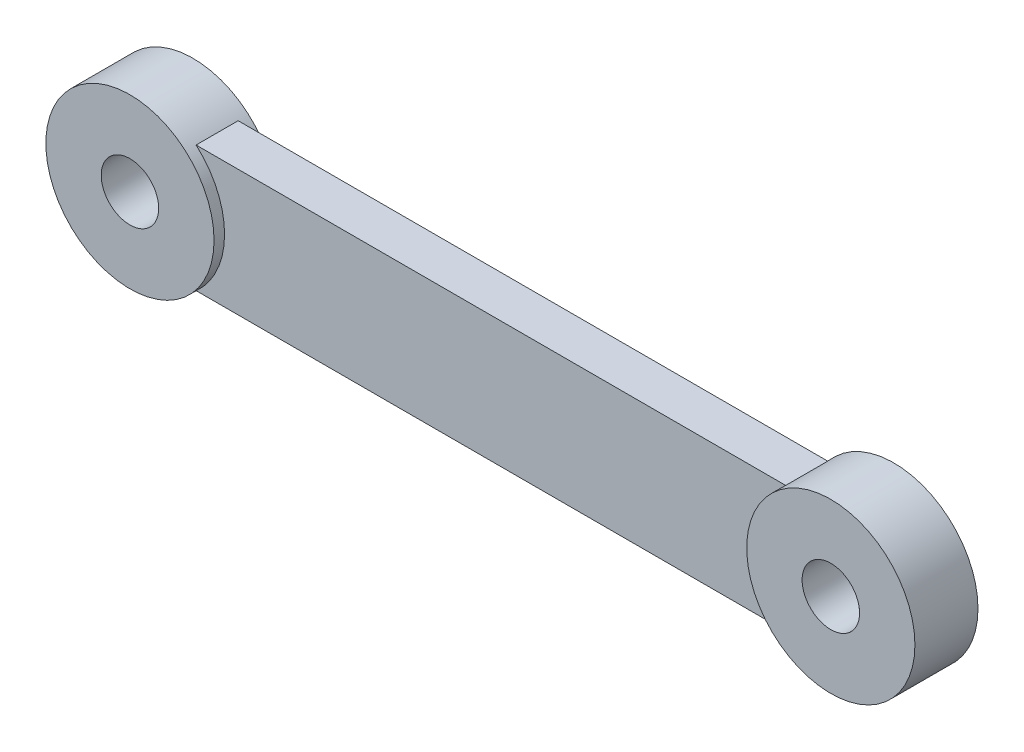
SolidWorks part; units mm, degrees
ref_plane "前视基准面" through (0, 0, 0) normal (0, 0, 1) x (1, 0, 0)
ref_plane "上视基准面" through (0, 0, 0) normal (0, 1, 0) x (1, 0, 0)
ref_plane "右视基准面" through (0, 0, 0) normal (1, 0, 0) x (0, 0, -1)
other "Configuration Table"
sketch "草图1" plane through (0, 0, 0) normal (0, 0, 1) x (1, 0, 0)
  line L0 (-50, -9) -> (-42.0627, -9) construction
  line L1 (-42.0627, 9) -> (42.0627, 9)
  line L2 (-50, 9) -> (-50, -9) construction
  line L3 (-42.0627, -9) -> (42.0627, -9)
  line L4 (50, 9) -> (50, -9) construction
  line L5 (-50, 9) -> (50, -9) construction
  line L6 (-50, -9) -> (50, 9) construction
  line L7 (-50, 9) -> (-42.0627, 9) construction
  line L8 (42.0627, 9) -> (50, 9) construction
  line L9 (42.0627, -9) -> (50, -9) construction
  circle A0 centre (-50, 0) radius 12
  circle A1 centre (-50, 0) radius 4.1
  circle A2 centre (50, 0) radius 12
  circle A3 centre (50, 0) radius 4.1
  point P0 (0, 0)
  dimension "D3" = 24
  dimension "D4" = 8.2
  dimension "D5" = 24
  dimension "D6" = 8.2
  dimension "D1" = 100
  dimension "D2" = 18
extrude "凸台-拉伸1" add sketch "草图1" along normal blind 3 and the other way blind 3 contours A2 L1 A0 L3 region at (0, 0, 0)
extrude "凸台-拉伸2" add sketch "草图1<4>" along normal mid plane 9 contours A0 A1 | A2 A3 region at (-39.3721, 4.7976, 0) region at (54.7976, 10.6279, 0)
sketch "草图1<4>" plane through (0, 0, 0) normal (0, 0, 1) x (1, 0, 0) same geometry as "草图1"
